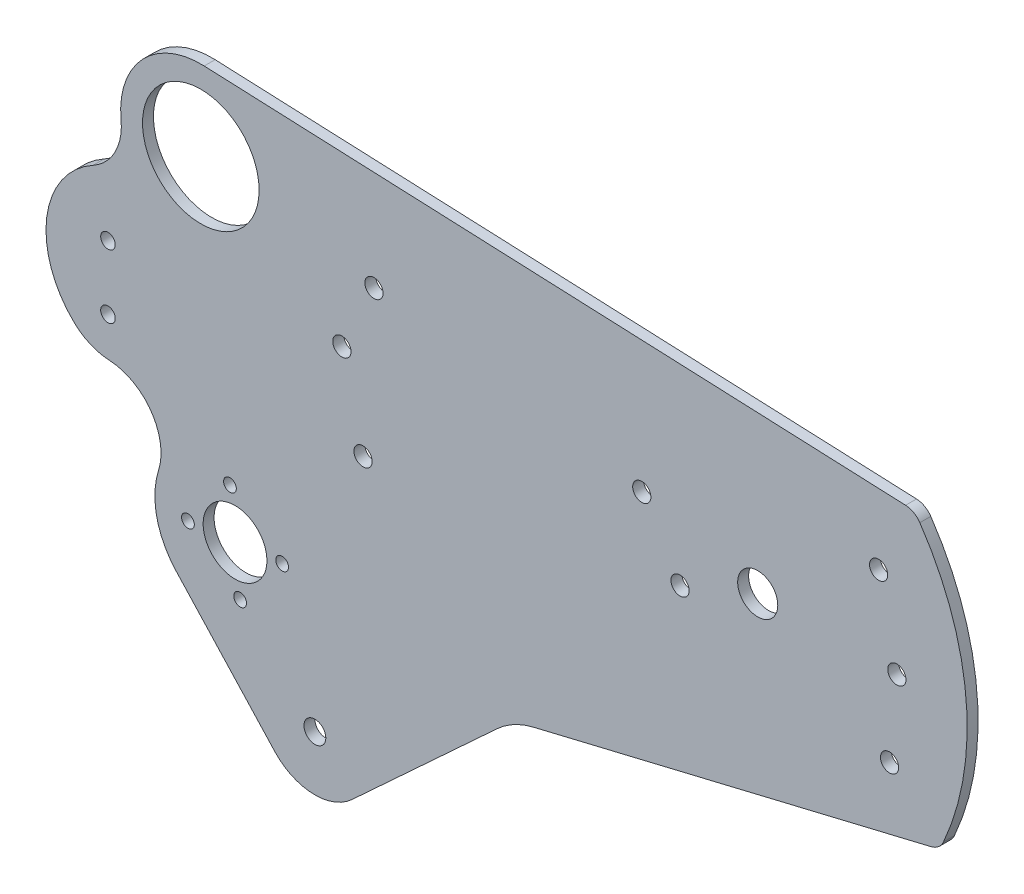
SolidWorks part; units mm, degrees
ref_plane "Front Plane" through (0, 0, 0) normal (0, 0, 1) x (1, 0, 0)
ref_plane "Top Plane" through (0, 0, 0) normal (0, 1, 0) x (1, 0, 0)
ref_plane "Right Plane" through (0, 0, 0) normal (1, 0, 0) x (0, 0, -1)
sketch "Sketch1" plane through (0, 0, 0) normal (0, 0, 1) x (1, 0, 0)
  line L0 (86.8854, -33.5) -> (-137.2004, -33.5) construction
  line L1 (-111.886, 49.4802) -> (80.595, 41.3179)
  line L2 (-115.2069, 49.6211) -> (-101.035, -81.6153) construction
  line L3 (-97.8208, -80.7688) -> (92.1699, -30.731) construction
  line L4 (78.7977, 41.3942) -> (86.7407, -32.1609) construction
  line L5 (-108.121, -15.9971) -> (82.7692, 4.6166) construction
  line L6 (91, -33.5) -> (-88.5, -33.5) construction
  line L7 (-97.4673, 5.5) -> (-155.3054, 5.5) construction
  line L8 (-138.3, -14) -> (-155.3054, -14) construction
  line L9 (-138.3, 5.5) -> (-138.3, -33.5) construction
  line L10 (-155.3054, 5.5) -> (-155.3054, -33.5) construction
  line L11 (40.0178, 33.5) -> (40.0178, -33.5) construction
  line L12 (-101.0425, -81.5467) -> (-90.8208, -79.0963)
  line L13 (-91.5, 33.5) -> (88, 33.5) construction
  line L14 (-68.3, -21.5) -> (-107.0746, -25.6872) construction
  line L15 (-138.3, -5.25) -> (-81.5148, -93.5701) construction
  line L17 (-119.5948, -74.4106) -> (-92.5405, -103.7404)
  line L18 (-71.3446, -104.5958) -> (-31.4414, -67.7885)
  line L19 (-21.4819, -62.4739) -> (87.5999, -36.3241)
  circle A0 centre (40.0178, 0) radius 5.5
  circle A1 centre (-112.8181, 27.5) radius 13 construction
  circle A2 centre (-103.4238, -59.4942) radius 13 construction
  arc A3 (-91.5, 33.5) -> (-88.5, -33.5) centre (-18.0922, 3.2198) ccw construction
  circle A4 centre (-68.3, -21.5) radius 2.5
  circle A5 centre (-68.3, -21.5) radius 2.5 construction
  circle A6 centre (-138.3, -5.25) radius 2
  circle A7 centre (-138.3, -22.75) radius 2
  arc A8 (-142.3827, 10.6321) -> (-147.5429, -29.3643) centre (-130.3054, -11.2571) ccw
  arc A9 (-147.5429, -29.3643) -> (-137.2004, -33.5) centre (-137.2004, -18.5) ccw
  circle A10 centre (-112.8181, 27.5) radius 22
  arc A11 (87.5999, -36.3241) -> (91, -33.5) centre (86.4343, -31.4619) ccw
  circle A12 centre (-103.4238, -59.4942) radius 22
  arc A13 (91, -33.5) -> (84.5157, 39.1371) centre (22.6589, -2.9929) ccw
  arc A14 (91, -33.5) -> (88, 33.5) centre (22.6589, -2.9929) ccw construction
  arc A15 (84.5157, 39.1371) -> (80.595, 41.3179) centre (80.3831, 36.3224) ccw
  arc A17 (-124.4228, -52.9336) -> (-137.9704, -33.4802) centre (-138.7403, -48.4604) ccw
  arc A18 (-142.3827, 10.6321) -> (-134.7058, 25.2795) centre (-149.6292, 23.7656) ccw
  circle A19 centre (-74.1, 1.7) radius 2.5
  circle A20 centre (-65.3, 20) radius 2.5
  circle A21 centre (8.2, 8.3) radius 2.5
  circle A23 centre (18.7, -8.7) radius 2.5
  circle A25 centre (78.2, -0.1) radius 2.5
  circle A26 centre (76.2, -22) radius 2.5
  circle A27 centre (73.2, 22.3) radius 2.5
  circle A28 centre (73.2, 22.3) radius 2.5 construction
  circle A29 centre (78.2, -0.1) radius 2.5 construction
  circle A30 centre (-81.5148, -93.5701) radius 3
  circle A31 centre (8.2, 8.3) radius 2.5 construction
  circle A32 centre (18.7, -8.7) radius 2.5 construction
  circle A33 centre (76.2, -22) radius 2.5 construction
  circle A34 centre (-74.1, 1.7) radius 2.5 construction
  circle A35 centre (-65.3, 20) radius 2.5 construction
  circle A36 centre (-114.2138, 40.4249) radius 1.75
  circle A37 centre (-99.8933, 28.8957) radius 1.75
  circle A38 centre (-111.4224, 14.5751) radius 1.75
  circle A39 centre (-125.743, 26.1043) radius 1.75
  circle A40 centre (-104.8196, -46.5694) radius 1.75
  circle A41 centre (-90.499, -58.0985) radius 1.75
  circle A42 centre (-102.0281, -72.4191) radius 1.75
  circle A43 centre (-116.3487, -60.89) radius 1.75
  circle A44 centre (40.0178, 0) radius 35 construction
  circle A45 centre (40.0178, 0) radius 43
  circle A49 centre (-103.4238, -59.4942) radius 16
  circle A50 centre (-112.8181, 27.5) radius 16
  circle A51 centre (-112.8181, 27.5) radius 8.75
  circle A52 centre (-103.4238, -59.4942) radius 8.75
  arc A53 (91, -33.5) -> (88, 33.5) centre (22.6589, -2.9929) ccw construction
  arc A54 (-92.5405, -103.7404) -> (-71.3446, -104.5958) centre (-81.5148, -93.5701) ccw
  arc A55 (-21.4819, -62.4739) -> (-31.4414, -67.7885) centre (-16.2632, -84.2433) ccw
  point P44 (-89.5048, -109.3086)
  point P52 (82.7692, 4.6166)
  point P109 (-112.8181, 27.5)
  point P118 (-103.4238, -59.4942)
  point P134 (-3.1394, -57.9912)
  dimension "D5" = 4
  dimension "D6" = 25
  dimension "D9" = 15
  dimension "D13" = 10
  dimension "D14" = 26
  dimension "D11" = 44
  dimension "D15" = 3.5
  dimension "D12" = 70
  dimension "D19" = 11
  dimension "D20" = 17.5
  dimension "D22" = 32
  dimension "D24" = 6
  dimension "D2" = 39
  dimension "D3" = 70
  dimension "D4" = 17.5
  dimension "D7" = 14
  dimension "D8" = 10
  dimension "D10" = 87.5
  dimension "D21" = 192
  dimension "D23" = 39
  dimension "D25" = 105
  dimension "D18" = 8
  dimension "D16" = 4
  dimension "D17" = 4
extrude "Boss-Extrude1" add sketch "Sketch1" along normal blind 3 contours A45 A0 A25 A26 A27 | A45 L1 A10 A18 A8 A9 A17 A12 L3 A23 A21 A20 A19 A7 A6 A4 | A12 A49 | A10 A50 | A49 A52 A40 A41 A42 A43 region at (70.1828, 28.9129, 0) region at (-46.6317, -16.6745, 0) region at (-97.3849, 42.2927, 0) region at (-100.1994, -38.3611, 0) region at (-118.9713, -59.4942, 0)
